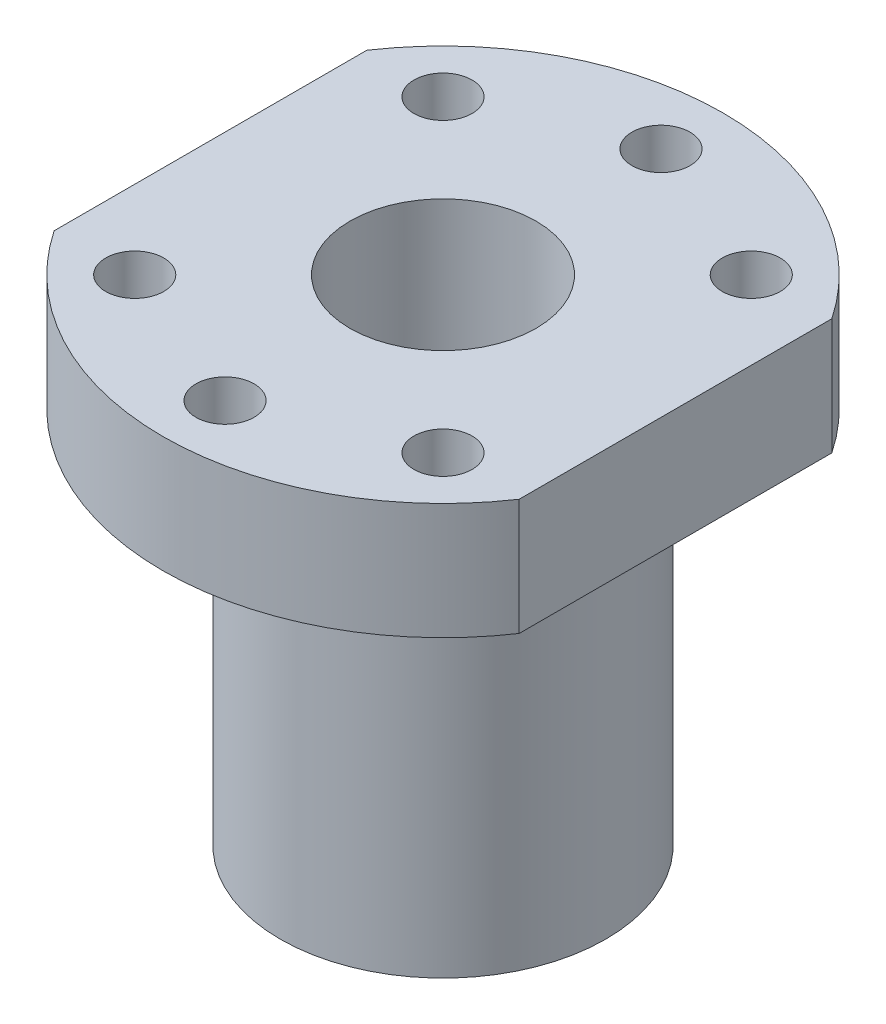
SolidWorks part; units mm, degrees
ref_plane "Front Plane" through (0, 0, 0) normal (0, 0, 1) x (1, 0, 0)
ref_plane "Top Plane" through (0, 0, 0) normal (0, 1, 0) x (1, 0, 0)
ref_plane "Right Plane" through (0, 0, 0) normal (1, 0, 0) x (0, 0, -1)
sketch "Sketch1" plane through (0, 0, 0) normal (0, 1, 0) x (1, 0, 0)
  line L1 (-20, 33.2385) -> (20, 33.2385)
  line L2 (-20, 33.2385) -> (-20, -33.2385)
  line L3 (-20, -33.2385) -> (20, -33.2385)
  line L4 (20, 33.2385) -> (20, -33.2385)
  line L5 (-20, 33.2385) -> (20, -33.2385) construction
  line L6 (-20, -33.2385) -> (20, 33.2385) construction
  circle A0 centre (0, 0) radius 24.1
  circle A1 centre (0, 0) radius 14
  circle A2 centre (0, 0) radius 8
  dimension "D1" = 28
  dimension "D2" = 48.2
  dimension "D4" = 16
  dimension "D3" = 40
extrude "Boss-Extrude1" add sketch "Sketch1" along normal blind 10 contours L4 A0 L2 A1 | A1 A2 region at (0, 0, -23.4736) region at (-13.604, 0, 0)
extrude "Boss-Extrude2" add sketch "Sketch1<3>" against normal blind 32.5 contours A1 A2 region at (-13.604, 0, 0)
sketch "Sketch1<3>" plane through (0, 0, 0) normal (0, 1, 0) x (1, 0, 0) same geometry as "Sketch1"
sketch "Sketch2" plane through (0, 10, 0) normal (0, 1, 0) x (1, 0, 0)
  circle A0 centre (0, 0) radius 18.75 construction
  circle A1 centre (0, -18.75) radius 2.5
  circle A2 centre (-13.2583, -13.2583) radius 2.5
  circle A3 centre (-18.75, 0) radius 2.5 [skipped]
  circle A4 centre (-13.2583, 13.2583) radius 2.5
  circle A5 centre (0, 18.75) radius 2.5
  circle A6 centre (13.2583, 13.2583) radius 2.5
  circle A7 centre (18.75, 0) radius 2.5 [skipped]
  circle A8 centre (13.2583, -13.2583) radius 2.5
  point P22 (0, 0)
  dimension "D1" = 37.5
  dimension "D2" = 5
  dimension "D3" = 8
extrude "Cut-Extrude1" cut sketch "Sketch2" against normal blind 32.5
